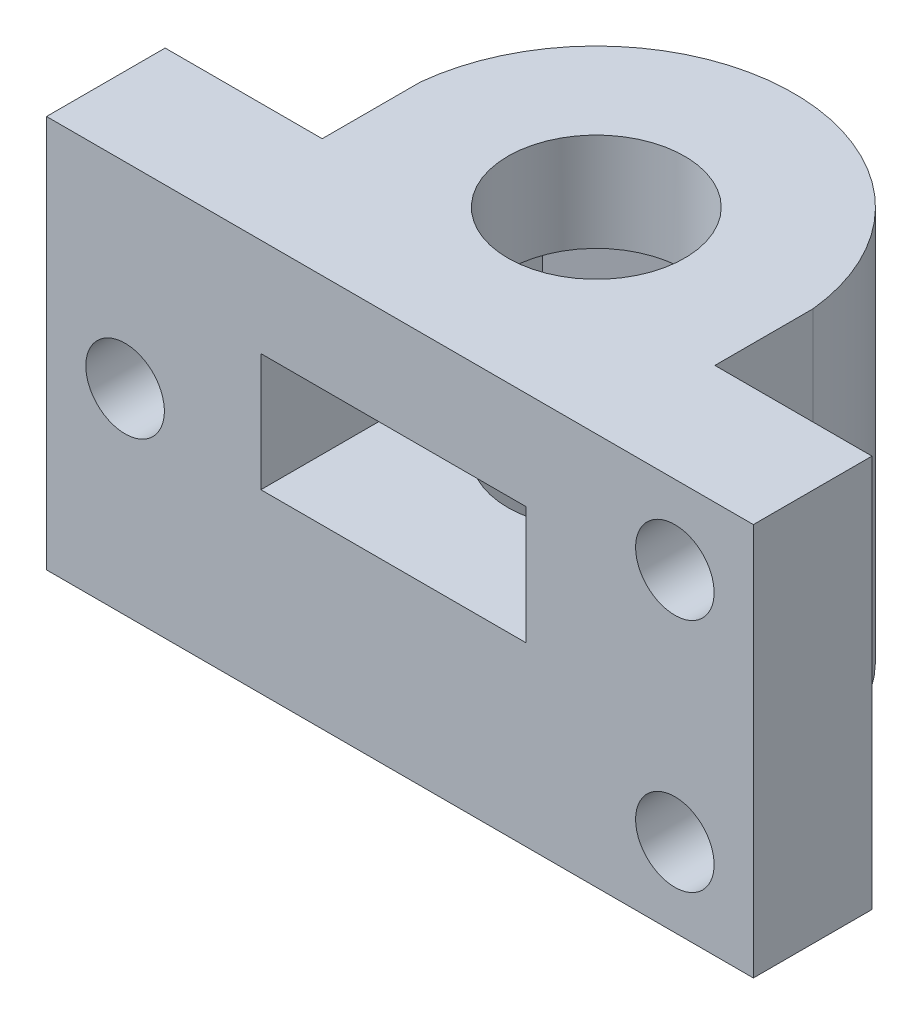
SolidWorks part; units mm, degrees
material "Copper"
ref_plane "Front Plane" through (0, 0, 0) normal (0, 0, 1) x (1, 0, 0)
ref_plane "Top Plane" through (0, 0, 0) normal (0, 1, 0) x (1, 0, 0)
ref_plane "Right Plane" through (0, 0, 0) normal (1, 0, 0) x (0, 0, -1)
sketch "Sketch1" plane through (0, 0, 0) normal (0, 1, 0) x (1, 0, 0)
  line L0 (0, 0) -> (20, 0)
  line L1 (0, 11.04) -> (0, 6.04)
  line L2 (20, 6.04) -> (20, 11.04)
  line L3 (0, 0) -> (-8, 0)
  line L4 (-8, 0) -> (-8, 6.04)
  line L5 (-8, 6.04) -> (0, 6.04)
  line L6 (20, 0) -> (28, 0)
  line L7 (28, 0) -> (28, 6.04)
  line L8 (28, 6.04) -> (20, 6.04)
  circle A0 centre (10, 10) radius 4.5
  arc A1 (0, 11.04) -> (20, 11.04) centre (10, 10) cw
  dimension "D1" = 10
  dimension "D2" = 5
  dimension "D3" = 9
  dimension "D4" = 5
extrude "Boss-Extrude1" add sketch "Sketch1" along normal blind 20
ref_plane "Plane1" through (0, 15, 0) normal (0, 1, 0) x (1, 0, 0)
sketch "Sketch4" plane through (0, 15, 0) normal (0, 1, 0) x (1, 0, 0)
  line L0 (10, 10) -> (10, -3.0938) construction
  line L2 (10, 2.4944) -> (16.5, 6.2472)
  line L3 (16.5, 6.2472) -> (16.5, 13.7528)
  line L4 (16.5, 13.7528) -> (10, 17.5056)
  line L5 (10, 17.5056) -> (3.5, 13.7528)
  line L6 (3.5, 13.7528) -> (3.5, 6.2472)
  line L7 (3.5, 6.2472) -> (10, 2.4944)
  circle A0 centre (10, 10) radius 6.5 construction
extrude "Cut-Extrude2" cut sketch "Sketch4" against normal blind 6
sketch "Sketch9" plane through (0, 0, -6.04) normal (0, 0, -1) x (-1, 0, 0)
  line L0 (-28, 20) -> (-28, 0) construction
  line L1 (-28, 0) -> (-20, 0) construction
  line L2 (-28, 20) -> (-20, 20) construction
  line L3 (8, 20) -> (8, 0) construction
  line L4 (0, 20) -> (8, 20) construction
  circle A0 centre (-24, 4) radius 2
  circle A1 centre (-24, 16) radius 2
  circle A2 centre (4, 10) radius 2
  dimension "D1" = 4
  dimension "D5" = 4
  dimension "D2" = 4
  dimension "D3" = 4
  dimension "D4" = 4
  dimension "D6" = 10
extrude "Cut-Extrude4" cut sketch "Sketch9" against normal through all
ref_plane "Plane7" through (0, 0, -6.2472) normal (0, 0, -1) x (-1, 0, 0)
sketch "Sketch10" plane through (0, 0, -6.2472) normal (0, 0, -1) x (-1, 0, 0)
  line L1 (-2.9173, 8.9958) -> (-16.4104, 8.9958)
  line L2 (-2.9173, 8.9958) -> (-2.9173, 15.0012)
  line L3 (-2.9173, 15.0012) -> (-16.4104, 15.0012)
  line L4 (-16.4104, 8.9958) -> (-16.4104, 15.0012)
extrude "Cut-Extrude5" cut sketch "Sketch10" against normal blind 10
